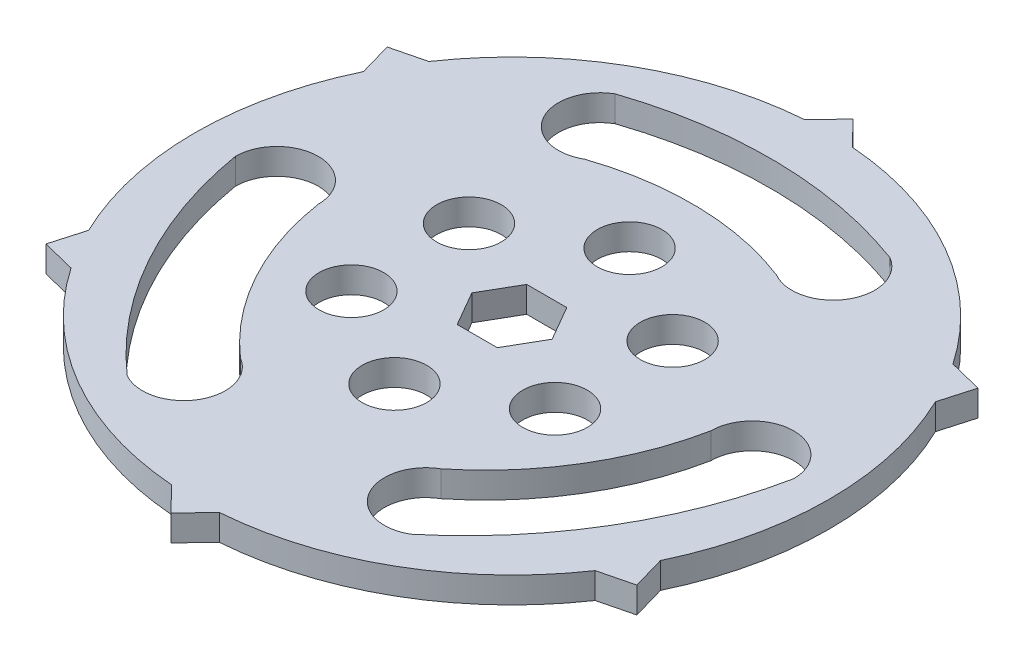
SolidWorks part; units mm, degrees
ref_plane "Front Plane" through (0, 0, 0) normal (0, 0, 1) x (1, 0, 0)
ref_plane "Top Plane" through (0, 0, 0) normal (0, 1, 0) x (1, 0, 0)
ref_plane "Right Plane" through (0, 0, 0) normal (1, 0, 0) x (0, 0, -1)
sketch "Sketch2" plane through (0, 0, 0) normal (0, 1, 0) x (1, 0, 0)
  line L0 (0, 8.2082) -> (0, 14.4741) construction
  line L1 (0, -16.2331) -> (0, -11.3412)
  line L2 (9.8217, 5.6706) -> (9.8217, -5.6706) construction
  line L3 (0, -11.3412) -> (9.8217, -5.6706) construction
  line L4 (4.9109, -8.5059) -> (17.7739, -30.7853) construction
  line L5 (9.8217, -5.6706) -> (9.8217, 0)
  line L6 (9.8217, 0) -> (36.5315, 0) construction
  line L7 (0, 0) -> (0, 30.6059)
  line L8 (0, 32.907) -> (2.3065, 30.5188)
  line L13 (0.6206, 45.2548) -> (0.0934, 32.8103) construction
  line L14 (-0.0557, 32.8493) -> (0, 30.6059) construction
  line L15 (0, 32.907) -> (-2.3065, 30.5188)
  line L16 (28.4983, 16.4535) -> (27.5833, 13.2619)
  line L17 (28.4983, 16.4535) -> (25.2768, 17.2569)
  line L22 (28.4983, -16.4535) -> (25.2768, -17.2569)
  line L23 (28.4983, -16.4535) -> (27.5833, -13.2619)
  line L28 (0, -32.907) -> (-2.3065, -30.5188)
  line L29 (0, -32.907) -> (2.3065, -30.5188)
  line L34 (-28.4983, -16.4535) -> (-27.5833, -13.2619)
  line L35 (-28.4983, -16.4535) -> (-25.2768, -17.2569)
  line L40 (-28.4983, 16.4535) -> (-25.2768, 17.2569)
  line L41 (-28.4983, 16.4535) -> (-27.5833, 13.2619)
  line L43 (3.87, 0) -> (1.935, 3.3515)
  line L44 (1.935, 3.3515) -> (-1.935, 3.3515)
  line L45 (-1.935, 3.3515) -> (-3.87, 0)
  line L46 (-3.87, 0) -> (-1.935, -3.3515)
  line L47 (-1.935, -3.3515) -> (1.935, -3.3515)
  line L48 (1.935, -3.3515) -> (3.87, 0)
  arc A2 (2.3065, -30.5188) -> (25.2768, -17.2569) centre (0, 0) ccw
  circle A4 centre (0, 11.3412) radius 3.1171
  circle A5 centre (9.8217, 5.6706) radius 3.1171
  circle A6 centre (9.8217, -5.6706) radius 3.1171
  circle A7 centre (0, -11.3412) radius 3.1171
  circle A8 centre (-9.8217, -5.6706) radius 3.1171
  circle A9 centre (-9.8217, 5.6706) radius 3.1171
  arc A11 (9.3424, -16.1815) -> (13.3424, -23.1097) centre (11.3424, -19.6456) ccw
  arc A12 (27.1766, 0) -> (19.1766, 0) centre (23.1766, 0) ccw
  arc A13 (9.3424, -16.1815) -> (19.1766, 0) centre (-7.9186, 5.3879) ccw
  arc A14 (13.3424, -23.1097) -> (27.1766, 0) centre (-12.3902, 7.9904) ccw
  arc A15 (-18.6848, 0) -> (-26.6848, 0) centre (-22.6848, 0) ccw
  arc A16 (-26.6848, 0) -> (-13.5883, -23.5356) centre (13.115, 6.7351) ccw
  arc A17 (-13.5883, -23.5356) -> (-9.5883, -16.6074) centre (-11.5883, -20.0715) ccw
  arc A18 (-18.6848, 0) -> (-9.5883, -16.6074) centre (8.6254, 4.1638) ccw
  arc A19 (9.3424, 16.1815) -> (13.3424, 23.1097) centre (11.3424, 19.6456) ccw
  arc A20 (13.3424, 23.1097) -> (-13.5883, 23.5356) centre (-0.7247, -14.7255) ccw
  arc A21 (-13.5883, 23.5356) -> (-9.5883, 16.6074) centre (-11.5883, 20.0715) ccw
  arc A22 (9.3424, 16.1815) -> (-9.5883, 16.6074) centre (-0.7068, -9.5517) ccw
  arc A23 (27.5833, -13.2619) -> (27.5833, 13.2619) centre (0, 0) ccw
  arc A24 (25.2768, 17.2569) -> (2.3065, 30.5188) centre (0, 0) ccw
  arc A25 (-2.3065, 30.5188) -> (-25.2768, 17.2569) centre (0, 0) ccw
  arc A26 (-27.5833, 13.2619) -> (-27.5833, -13.2619) centre (0, 0) ccw
  arc A27 (-25.2768, -17.2569) -> (-2.3065, -30.5188) centre (0, 0) ccw
  circle A28 centre (0, 0) radius 3.3515 construction
  point P1 (5.6103, 1.9774)
  point P23 (0, 0)
  point P52 (0, 0)
  point P53 (6.7578, 0)
  point P54 (0, 0)
  point P56 (0, -40.9329)
  point P58 (0, -32.907)
  point P95 (0, 0)
  dimension "D2" = 8
  dimension "D3" = 8
  dimension "D5" = 3.87
  dimension "D1" = 6
  dimension "D4" = 3
  dimension "D7" = 6
extrude "Boss-Extrude2" add sketch "Sketch2" along normal blind 2.5 contours L41 A26 L34 L35 A27 L28 L29 A2 L22 L23 A23 L16 L17 A24 L8 L15 A25 L40 | A15 A16 A17 A18 | A8 | A9 | A7 | A6 | A5 | A11 A14 A12 A13 | A19 A20 A21 A22 | A4 | L43 L44 L45 L46 L47 L48
